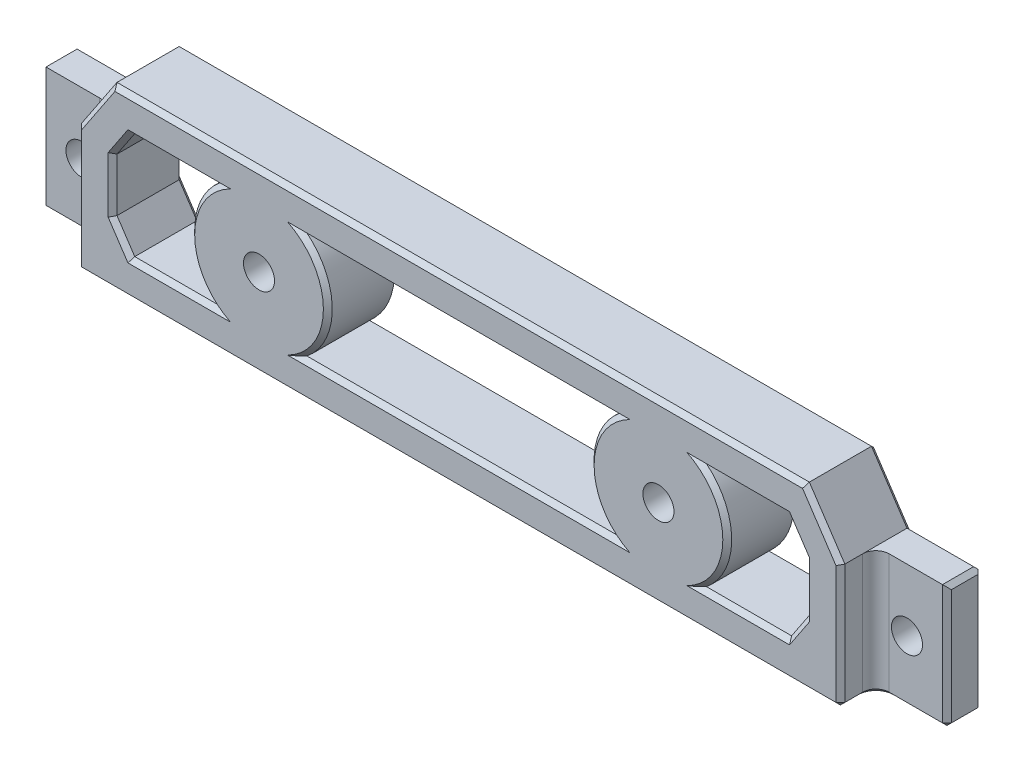
SolidWorks part; units mm, degrees
ref_plane "Front Plane" through (0, 0, 0) normal (0, 0, 1) x (1, 0, 0)
ref_plane "Top Plane" through (0, 0, 0) normal (0, 1, 0) x (1, 0, 0)
ref_plane "Right Plane" through (0, 0, 0) normal (1, 0, 0) x (0, 0, -1)
sketch "Sketch2" plane through (0, 0, 0) normal (0, 1, 0) x (1, 0, 0)
  line L12 (8, 0) -> (8, -4)
  line L13 (8, -4) -> (94, -4)
  line L14 (51, -4) -> (51, 4) construction
  line L16 (102, 4) -> (0, 4) construction
  line L17 (94, 0) -> (94, -4)
  line L27 (0, 4) -> (0, 0)
  line L28 (0, 0) -> (8, 0)
  line L29 (0, 4) -> (102, 4)
  line L30 (102, 4) -> (102, 0)
  line L31 (102, 0) -> (94, 0)
  dimension "D1" = 8
  dimension "D2" = 4
  dimension "D3" = 86
  dimension "D4" = 8
extrude "Boss-Extrude2" add sketch "Sketch2" along normal blind 20
sketch "Sketch3" plane through (0, 0, 4) normal (0, 0, 1) x (1, 0, 0)
  line L0 (8, 20) -> (94, 20) construction
  line L3 (8, 20) -> (8, 0) construction
  line L4 (94, 20) -> (94, 0) construction
  circle A0 centre (28.5, 10) radius 1.75
  circle A1 centre (73.5, 10) radius 1.75
  dimension "D1" = 3.5
  dimension "D2" = 3.5
  dimension "D4" = 20.5
  dimension "D3" = 20.5
  dimension "D5" = 10
extrude "Cut-Extrude1" cut sketch "Sketch3" against normal up to next
sketch "Sketch6" plane through (0, 0, 4) normal (0, 0, 1) x (1, 0, 0)
  line L4 (23.5946, 16) -> (12, 16)
  line L5 (33.4054, 4) -> (68.5946, 4)
  line L6 (78.4054, 4) -> (90, 4)
  line L7 (68.5946, 16) -> (33.4054, 16)
  line L8 (12, 4) -> (90, 4)
  line L9 (90, 4) -> (90, 16)
  line L10 (90, 16) -> (12, 16)
  line L11 (12, 16) -> (12, 4)
  line L12 (12, 4) -> (23.5946, 4)
  line L13 (90, 4) -> (90, 16)
  line L14 (90, 16) -> (78.4054, 16)
  line L15 (12, 16) -> (12, 4)
  circle A3 centre (28.5, 10) radius 7.75
  arc A4 (23.5946, 16) -> (23.5946, 4) centre (28.5, 10) ccw
  arc A5 (33.4054, 4) -> (33.4054, 16) centre (28.5, 10) ccw
  circle A6 centre (73.5, 10) radius 7.75
  arc A7 (78.4054, 4) -> (78.4054, 16) centre (73.5, 10) ccw
  arc A8 (68.5946, 16) -> (68.5946, 4) centre (73.5, 10) ccw
  dimension "D1" = 6
  dimension "D2" = 6
  dimension "D3" = 4
extrude "Cut-Extrude3" cut sketch "Sketch6" against normal up to next
sketch "Sketch10" plane through (0, 20, 0) normal (0, 1, 0) x (1, 0, 0)
  line L1 (0, 4) -> (8, 4)
  line L2 (0, 4) -> (0, 0)
  line L3 (0, 0) -> (8, 0)
  line L4 (8, 4) -> (8, 0)
  line L5 (102, 4) -> (94, 4)
  line L6 (102, 4) -> (102, 0)
  line L7 (102, 0) -> (94, 0)
  line L8 (94, 4) -> (94, 0)
extrude "Cut-Extrude7" cut sketch "Sketch10" against normal blind 6
sketch "Sketch11" plane through (0, 0, 0) normal (0, 0, 1) x (1, 0, 0)
  line L0 (0, 0) -> (8, 0) construction
  line L3 (0, 14) -> (0, 0) construction
  line L4 (51, 0) -> (51, 20) construction
  line L5 (8, 0) -> (94, 0) construction
  line L6 (8, 20) -> (94, 20) construction
  circle A0 centre (4.5, 7) radius 1.75
  circle A2 centre (97.5, 7) radius 1.75
  dimension "D1" = 4.5
  dimension "D2" = 3.5
  dimension "D3" = 7
extrude "Cut-Extrude8" cut sketch "Sketch11" against normal up to next
fillet "Fillet1" radius 1.5 2 edges at (94, 7, 0) (8, 7, 0)
sketch "Sketch12" plane through (0, 0, 4) normal (0, 0, -1) x (-1, 0, 0)
  text T0 "<b>3.0.1</b>" font "Century Gothic" height 3
extrude "Cut-Extrude9" [suppressed] cut sketch "Sketch12" along normal blind 0.5
sketch "Sketch13" plane through (0, 0, 4) normal (0, 0, 1) x (1, 0, 0)
  line L0 (8, 14) -> (12, 20)
  line L1 (8, 20) -> (8, 0) construction
  line L2 (8, 20) -> (94, 20) construction
  line L3 (12, 20) -> (8, 20)
  line L4 (8, 20) -> (8, 14)
  line L5 (90, 20) -> (94, 20)
  line L6 (94, 20) -> (94, 14)
  line L7 (94, 20) -> (94, 0) construction
  line L8 (94, 14) -> (90, 20)
  dimension "D1" = 4
  dimension "D2" = 6
  dimension "D3" = 4
  dimension "D4" = 6
extrude "Cut-Extrude10" cut sketch "Sketch13" against normal up to next
chamfer "Chamfer1" distance 0.5 angle 45 8 edges at (51, 20, -4) (10, 17, -4) (4, 14, -4) (0, 7, -4) (92, 17, -4) (98, 14, -4) (102, 7, -4) (51, 0, -4)
sketch "Sketch16" plane through (0, 0, 4) normal (0, 0, 1) x (1, 0, 0)
  line L0 (12, 13) -> (14, 16)
  line L1 (12, 16) -> (12, 4) construction
  line L2 (23.5946, 16) -> (12, 16) construction
  line L3 (14, 16) -> (12, 16)
  line L4 (12, 16) -> (12, 13)
  line L5 (8, 14) -> (12, 20) construction
  line L6 (51, 16) -> (51, 4) construction
  line L7 (68.5946, 16) -> (33.4054, 16) construction
  line L8 (33.4054, 4) -> (68.5946, 4) construction
  line L9 (88, 16) -> (90, 16)
  line L10 (90, 13) -> (88, 16)
  line L11 (90, 16) -> (90, 13)
  line L12 (12, 10) -> (90, 10) construction
  line L13 (90, 4) -> (90, 16) construction
  line L14 (90, 7) -> (88, 4)
  line L15 (90, 4) -> (90, 7)
  line L16 (88, 4) -> (90, 4)
  line L17 (14, 4) -> (12, 4)
  line L18 (12, 7) -> (14, 4)
  line L19 (12, 4) -> (12, 7)
  dimension "D1" = 2
extrude "Boss-Extrude3" add sketch "Sketch16" against normal up to surface (8 mm away) up to face at (51, 11.75, -4)
chamfer "Chamfer3" distance 0.5 angle 45 50 edges at (102, 0, -1.75) (102, 7, 0) (102, 14, -1.75) (0, 0, -1.75) (0, 7, 0) (0, 14, -1.75) (83.2027, 4, 4) (90, 10, 4) (83.2027, 16, 4) (81.25, 10, 4) (65.75, 10, 4) (51, 4, 4) (36.25, 10, 4) (51, 16, 4) (18.7973, 16, 4) (12, 10, 4) (20.75, 10, 4) (18.7973, 4, 4) (94, 7, 4) (92, 17, 4) (51, 0, 4) (8, 7, 4) (10, 17, 4) (51, 20, 4) (90, 10, -4) (83.2027, 4, -4) (83.2027, 16, -4) (81.25, 10, -4) (65.75, 10, -4) (51, 16, -4) (51, 4, -4) (36.25, 10, -4) (18.7973, 16, -4) (20.75, 10, -4) (18.7973, 4, -4) (12, 10, -4) (98.75, 0, 0) (94.4393, 0, 0.4393) (94, 0, 2.75) (8, 0, 2.75) (7.5607, 0, 0.4393) (3.25, 0, 0) (89, 14.5, 4) (89, 14.5, -4) (13, 14.5, -4) (13, 14.5, 4) (89, 5.5, 4) (13, 5.5, 4) (89, 5.5, -4) (13, 5.5, -4)
chamfer "Chamfer6" distance 4 angle 45 2 edges at (30.25, 10, -4) (75.25, 10, -4)
